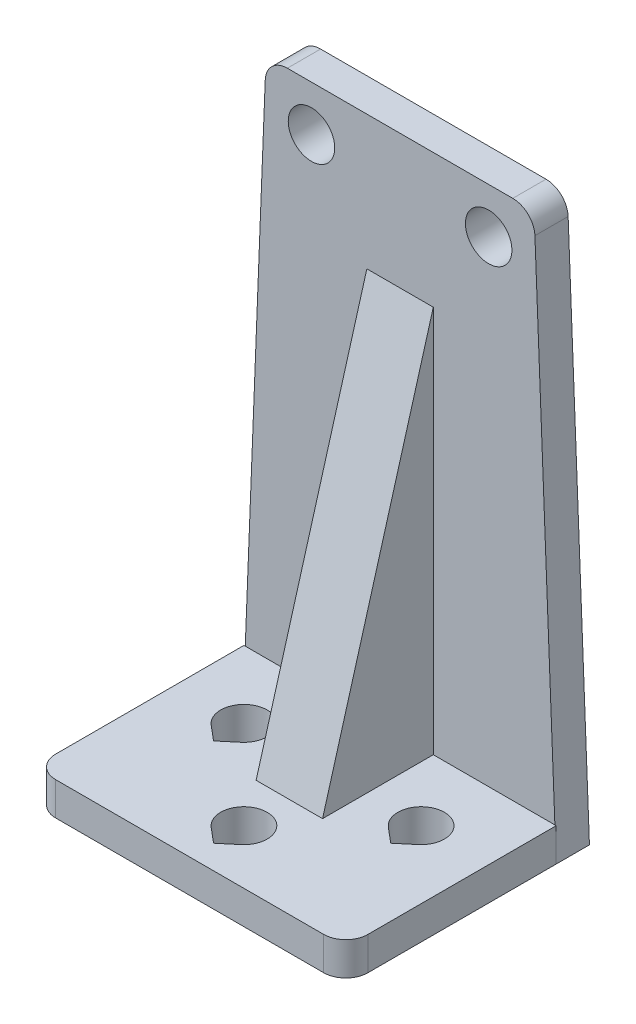
SolidWorks part; units mm, degrees
ref_plane "Front Plane" through (0, 0, 0) normal (0, 0, 1) x (1, 0, 0)
ref_plane "Top Plane" through (0, 0, 0) normal (0, 1, 0) x (1, 0, 0)
ref_plane "Right Plane" through (0, 0, 0) normal (1, 0, 0) x (0, 0, -1)
sketch "Sketch1" plane through (0, 0, 0) normal (0, 1, 0) x (1, 0, 0)
  line L0 (-8, -6.1) -> (8, -6.1) construction
  line L1 (-14.1, -19) -> (14.1, -19)
  line L2 (-14.1, -19) -> (-14.1, 0)
  line L3 (-14.1, 0) -> (14.1, 0)
  line L4 (14.1, -19) -> (14.1, 0)
  line L5 (-9.3499, -7.7087) -> (-8, -8.8414)
  line L6 (-8, -8.8414) -> (-6.6501, -7.7087)
  line L7 (-1.3499, -15.7087) -> (0, -16.8414)
  line L8 (0, -16.8414) -> (1.3499, -15.7087)
  line L9 (6.6501, -7.7087) -> (8, -8.8414)
  line L10 (8, -8.8414) -> (9.3499, -7.7087)
  arc A0 (-6.6501, -7.7087) -> (-9.3499, -7.7087) centre (-8, -6.1) ccw
  arc A1 (9.3499, -7.7087) -> (6.6501, -7.7087) centre (8, -6.1) ccw
  arc A2 (1.3499, -15.7087) -> (-1.3499, -15.7087) centre (0, -14.1) ccw
  point P4 (0, 0)
  point P10 (0, -6.1)
  dimension "D3" = 4.2
  dimension "D1" = 28.2
  dimension "D2" = 19
  dimension "D4" = 16
  dimension "D5" = 4
  dimension "D6" = 8
  dimension "D7" = 100
  dimension "D8" = 100
  dimension "D9" = 100
extrude "Boss-Extrude1" add sketch "Sketch1" along normal blind 3
sketch "Sketch2" plane through (0, 0, 0) normal (0, 0, -1) x (-1, 0, 0)
  line L0 (-8, 46) -> (8, 46) construction
  line L1 (-14.1, 0) -> (14.1, 0)
  line L2 (-14.1, 0) -> (-12.1, 50.1)
  line L3 (-12.1, 50.1) -> (12.1, 50.1)
  line L4 (14.1, 0) -> (12.1, 50.1)
  circle A0 centre (-8, 46) radius 2.1
  circle A1 centre (8, 46) radius 2.1
  point P5 (0, 46)
  point P12 (0, 50.1)
  dimension "D1" = 4.2
  dimension "D2" = 16
  dimension "D3" = 2
  dimension "D4" = 2
  dimension "D5" = 46
extrude "Boss-Extrude2" add sketch "Sketch2" along normal blind 3
sketch "Sketch3" plane through (0, 0, 0) normal (1, 0, 0) x (0, 0, -1)
  line L0 (0, 3) -> (-10, 3)
  line L1 (-19, 3) -> (0, 3) construction
  line L2 (-10, 3) -> (0, 38)
  line L3 (0, 50.1) -> (0, 3) construction
  line L4 (0, 38) -> (0, 3)
  dimension "D1" = 10
  dimension "D2" = 35
extrude "Boss-Extrude3" add sketch "Sketch3" along normal mid plane 6
fillet "Fillet1" radius 2 4 edges at (12.1, 50.1, -1.5) (-12.1, 50.1, -1.5) (14.1, 1.5, 19) (-14.1, 1.5, 19)
equation "\"width\"= 24"
equation "\"thk\"= 3"
equation "\"holesize\"= 4.2"
equation "\"holedistance\"= ( 20 + 12 ) / 2"
equation "\"threaded_hole\"= 3.9"
equation "\"fillet_radius\"= 2"
equation "\"ground_clearance\"= 25"
equation "\"tire_thk\"= 4"
equation "\"innerwheel_diam\" = \"wheel_diam\"-2*\"tire_thk\""
equation "\"innerwheel_thk\"= 8"
equation "\"wheel_diam\"= 2*(\"width\"/2+\"ground_clearance\")"
equation "\"coloursensor_holesize\"= 2.65"
equation "\"hole_to_edge\" = 4"
equation "\"D1@Sketch1\"=\"holedistance\"+ \"holesize\" + 2 * \"hole_to_edge\""
equation "\"D3@Sketch1\"=\"holesize\""
equation "\"D4@Sketch1\"=\"holedistance\""
equation "\"D6@Sketch1\"=\"holedistance\"/2"
equation "\"D5@Sketch1\"=\"hole_to_edge\""
equation "\"D1@Boss-Extrude1\"=\"thk\""
equation "\"D1@Sketch2\"=\"holesize\""
equation "\"D2@Sketch2\"=\"holedistance\""
equation "\"D4@Sketch2\"=\"D3@Sketch2\""
equation "\"D1@Boss-Extrude2\"=\"thk\""
equation "\"D1@Fillet1\"=\"fillet_radius\""
equation "\"D8@Sketch1\"=\"D7@Sketch1\""
equation "\"D9@Sketch1\"=\"D7@Sketch1\""
equation "\"D5@Sketch2\"=42 + \"thk\" + 1"
